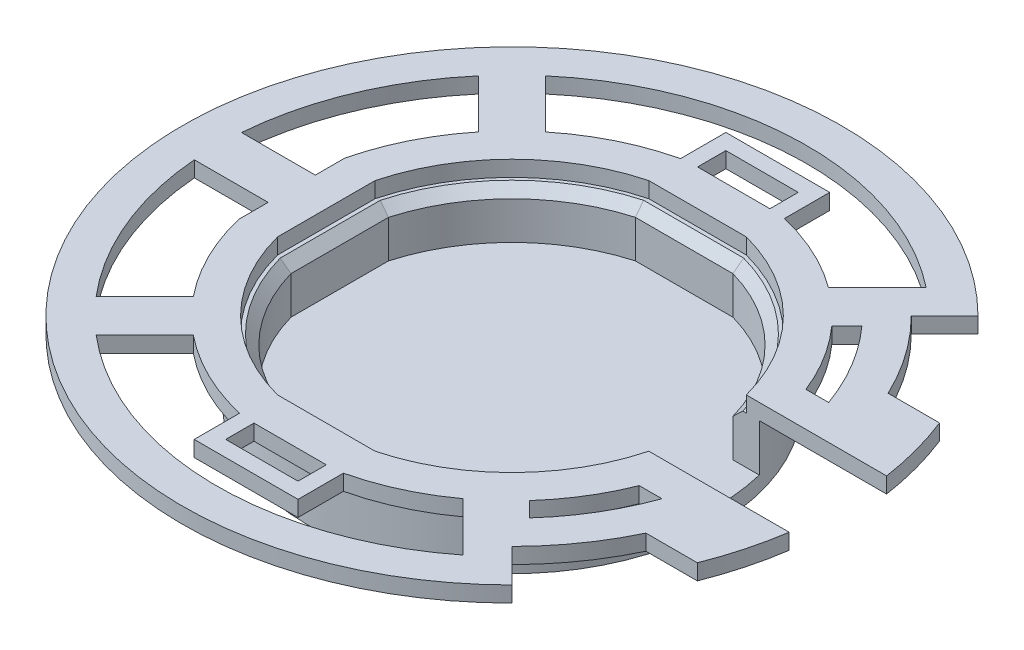
SolidWorks part; units mm, degrees
ref_plane "Front Plane" through (0, 0, 0) normal (0, 0, 1) x (1, 0, 0)
ref_plane "Top Plane" through (0, 0, 0) normal (0, 1, 0) x (1, 0, 0)
ref_plane "Right Plane" through (0, 0, 0) normal (1, 0, 0) x (0, 0, -1)
sketch "Front" plane through (0, 0, 0) normal (0, 0, 1) x (1, 0, 0)
  line L0 (0, 0) -> (0, 4407.3663) construction
  line L1 (0, 0) -> (4407.3663, 0) construction
  line L2 (0, 2.5) -> (-20.95, 2.5)
  line L3 (-20.95, 2.5) -> (-20.95, 1.5)
  line L4 (-20.95, 1.5) -> (-13, 1.5)
  line L5 (-13, 1.5) -> (-13, -2.5)
  line L6 (-13, -2.5) -> (0, -2.5)
  line L7 (0, -2.5) -> (0, 2.5)
  dimension "D1" = 1
  dimension "D2" = 41.9
  dimension "D3" = 5
  dimension "D4" = 26
sketch "Top" plane through (0, 0, 0) normal (0, 1, 0) x (1, 0, 0)
  line L0 (0, 0) -> (0, 50000) construction
  line L1 (0, 0) -> (50000, 0) construction
sketch "Right" plane through (0, 0, 0) normal (1, 0, 0) x (0, 0, -1)
  line L0 (0, 0) -> (0, 50000) construction
  line L1 (0, 0) -> (50000, 0) construction
revolve "Base" add sketch "Front" angle 360 about L0
sketch "Sketch2" plane through (0, 2.5, 0) normal (0, 1, 0) x (1, 0, 0)
  line L0 (0, 0) -> (50000, 0) construction
  line L1 (0, 0) -> (0, 50000) construction
  line L2 (-3.0984, 11.8) -> (3.0984, 11.8)
  line L3 (-11.8, -3.0984) -> (-11.8, 3.0984)
  line L4 (-3.0984, -11.8) -> (3.0984, -11.8)
  line L5 (11.8, -3.0984) -> (11.8, 3.0984)
  line L6 (-2.3, -14.1) -> (2.3, -14.1)
  line L7 (-2.3, 15.9) -> (2.3, 15.9)
  line L8 (-2.3, 15.9) -> (-2.3, 14.1)
  line L9 (-2.3, 14.1) -> (2.3, 14.1)
  line L10 (2.3, 15.9) -> (2.3, 14.1)
  line L11 (-2.3, 15.9) -> (2.3, 14.1) construction
  line L12 (-2.3, 14.1) -> (2.3, 15.9) construction
  line L13 (2.3, -15.9) -> (2.3, -14.1)
  line L14 (-2.3, -15.9) -> (2.3, -15.9)
  line L15 (-2.3, -15.9) -> (-2.3, -14.1)
  line L16 (-2.3, -14.1) -> (2.3, -15.9) construction
  line L17 (-2.3, -15.9) -> (2.3, -14.1) construction
  circle A0 centre (0, 0) radius 12.2 construction
  arc A1 (-11.8, 3.0984) -> (-3.0984, 11.8) centre (0, 0) cw
  arc A2 (-11.8, -3.0984) -> (-3.0984, -11.8) centre (0, 0) ccw
  arc A3 (11.8, -3.0984) -> (3.0984, -11.8) centre (0, 0) cw
  arc A4 (11.8, 3.0984) -> (3.0984, 11.8) centre (0, 0) ccw
  point P7 (0, 15)
  point P15 (-11.8, 0)
  point P16 (0, -11.8)
  point P19 (0, 11.8)
  point P28 (0, -15)
  dimension "D1" = 24.4
  dimension "D2" = 23.6
  dimension "D3" = 1.8
  dimension "D4" = 4.6
  dimension "D5" = 30
extrude "Watch Positioner" cut sketch "Sketch2" against normal up to surface (1 mm away) contours L5 A4 L2 A1 L3 A2 L4 A3 | L10 L7 L8 L9 | L15 L14 L13 L6 region at (0, 2.5, 0) region at (0, 2.5, 15) region at (0, 2.5, -15) up to face at (0, 1.5, -13)
sketch "Sketch4" plane through (0, 2.5, 0) normal (0, 1, 0) x (1, 0, 0)
  line L0 (3.0984, 11.8) -> (-3.0984, 11.8) construction
  line L1 (3.0984, 11.8) -> (-3.0984, 11.8) construction
  line L2 (-3.0984, 10.95) -> (-3.0984, 11.8) construction
  line L3 (3.0984, -10.95) -> (-3.0984, -10.95)
  line L4 (10.95, 3.0984) -> (10.95, -3.0984) construction
  line L5 (10.95, 3.0984) -> (21.95, 3.0984)
  line L6 (21.95, 3.0984) -> (21.95, -3.0984)
  line L7 (0, 0) -> (50000, 0) construction
  line L8 (0, 7.5051) -> (0, 50007.5051) construction
  line L9 (10.95, -3.0984) -> (21.95, -3.0984)
  line L10 (16.2153, 7.6984) -> (20.5557, 7.6984)
  line L12 (15.521, 15.521) -> (12.6926, 12.6926)
  line L13 (15.521, -15.521) -> (12.6926, -12.6926)
  line L14 (16.2153, -7.6984) -> (20.5557, -7.6984)
  line L15 (-10.95, 3.0984) -> (-10.95, -3.0984)
  line L18 (3.0984, 10.95) -> (-3.0984, 10.95)
  circle A0 centre (0, 0) radius 11.3799 construction
  arc A1 (-3.0984, -10.95) -> (-10.95, -3.0984) centre (0, 0) cw
  arc A2 (3.0984, -10.95) -> (10.95, -3.0984) centre (0, 0) ccw
  arc A3 (3.0984, 10.95) -> (10.95, 3.0984) centre (0, 0) cw
  arc A4 (15.521, 15.521) -> (20.5557, 7.6984) centre (0, 0) cw
  arc A5 (12.6926, -12.6926) -> (16.2153, -7.6984) centre (0, 0) ccw
  arc A6 (15.521, -15.521) -> (20.5557, -7.6984) centre (0, 0) ccw
  circle A7 centre (0, 0) radius 21.95
  circle A8 centre (0, 0) radius 21.95 construction
  arc A9 (12.6926, 12.6926) -> (16.2153, 7.6984) centre (0, 0) cw
  circle A10 centre (0, 0) radius 17.95
  circle A11 centre (0, 0) radius 17.95 construction
  arc A18 (-3.0984, 10.95) -> (-10.95, 3.0984) centre (0, 0) ccw
  point P13 (-10.95, 0)
  point P16 (0, -10.95)
  point P19 (0, 10.95)
  point P28 (21.95, 0)
  dimension "D1" = 22.7598
  dimension "D5" = 45
  dimension "D2" = 21.9
  dimension "D3" = 1
  dimension "D6" = 4.6
  dimension "D4" = 3
extrude "Watch Holder v2" cut sketch "Sketch4" against normal offset from surface (4 mm away) 1 up to face at (0, -2.5, -13)
chamfer "Chamfer1" distance 0.6 angle 45 7 edges at (8.0468, 1.5, 8.0468) (0, 1.5, 10.95) (-8.0468, 1.5, 8.0468) (-10.95, 1.5, 0) (-8.0468, 1.5, -8.0468) (0, 1.5, -10.95) (8.0468, 1.5, -8.0468)
sketch "Sketch5" plane through (0, 0, 0) normal (0, 1, 0) x (1, 0, 0)
  line L0 (3.3, 16.9) -> (3.3, 14.0168)
  line L1 (0, 0) -> (50000, 0) construction
  line L2 (0, 0) -> (0, 50000) construction
  line L6 (-14, 1.5) -> (-18.6899, 1.5)
  line L7 (0, 0) -> (35355.3391, -35355.3391) construction
  line L8 (0, 0) -> (35355.3391, 35355.3391) construction
  line L9 (9.4721, 12.5834) -> (8.5072, 11.6184)
  line L10 (8.5072, 11.6184) -> (10.7323, 9.6009) construction
  line L11 (10.7323, 9.6009) -> (11.6882, 10.5569)
  line L12 (-14.2764, 12.1551) -> (-11.1876, 9.0663)
  line L13 (-12.1551, 14.2764) -> (-9.0663, 11.1876)
  line L14 (-14.2764, -12.1551) -> (-11.1876, -9.0663)
  line L15 (-14, -1.5) -> (-14, -3.3705)
  line L16 (-14, -1.5) -> (-18.6899, -1.5)
  line L17 (9.4721, -12.5834) -> (11.611, -14.7223)
  line L18 (14.7591, -5.4984) -> (17.9257, -5.4984)
  line L19 (17.9858, -5.2984) -> (13.3898, -5.2984)
  line L20 (3.3705, -14) -> (-3.3705, -14)
  line L21 (-14, -3.3705) -> (-14, 3.3705)
  line L22 (-3.3705, 14) -> (3.3705, 14)
  line L23 (13.3898, 5.2984) -> (17.9858, 5.2984)
  line L24 (17.9257, 5.4984) -> (14.7591, 5.4984)
  line L25 (9.4721, 12.5834) -> (11.611, 14.7223)
  line L26 (11.611, -14.7223) -> (9.4721, -12.5834)
  line L30 (-14, 1.5) -> (-14, 3.3705)
  line L32 (13.3898, 5.2984) -> (14.832, 5.2984)
  line L34 (9.4721, 12.5834) -> (11.611, 14.7223)
  line L36 (9.4721, -12.5834) -> (8.5072, -11.6184)
  line L37 (3.3, -16.9) -> (3.3, -14.0168)
  line L38 (3.3, -16.9) -> (-3.3, -16.9)
  line L39 (-3.3, -16.9) -> (-3.3, -14.0168)
  line L40 (-12.1551, -14.2764) -> (-9.0663, -11.1876)
  line L41 (13.3898, -5.2984) -> (14.832, -5.2984)
  line L43 (10.7323, -9.6009) -> (11.6882, -10.5569)
  line L44 (-2.3, 15.9) -> (-3.3, 16.9) construction
  line L45 (2.3, 15.9) -> (2.3, 14.1) construction
  line L96 (-3.3, 16.9) -> (-3.3, 14.0168)
  line L97 (2.3, 15.9) -> (3.3, 16.9) construction
  line L104 (3.3, 16.9) -> (-3.3, 16.9)
  arc A0 (8.5072, 11.6184) -> (3.3, 14.0168) centre (0, 0) ccw
  arc A1 (-11.1876, 9.0663) -> (-14, 3.3705) centre (0, 0) ccw
  arc A2 (-14.2764, 12.1551) -> (-18.6899, 1.5) centre (0, 0) ccw
  arc A3 (-11.1876, -9.0663) -> (-14, -3.3705) centre (0, 0) cw
  arc A4 (-14.2764, -12.1551) -> (-18.6899, -1.5) centre (0, 0) cw
  arc A5 (8.5072, -11.6184) -> (3.3, -14.0168) centre (0, 0) cw
  arc A6 (-3.3, -14.0168) -> (-9.0663, -11.1876) centre (0, 0) cw
  arc A7 (11.611, -14.7223) -> (-12.1551, -14.2764) centre (0, 0) cw
  arc A8 (13.3898, -5.2984) -> (10.7323, -9.6009) centre (0, 0) cw
  arc A10 (14.832, -5.2984) -> (11.6882, -10.5569) centre (0, 0) cw
  arc A18 (9.4721, -12.5834) -> (14.7591, -5.4984) centre (0, 0) ccw
  arc A19 (17.9257, -5.4984) -> (17.9858, -5.2984) centre (0, 0) ccw
  arc A20 (3.3705, -14) -> (13.3898, -5.2984) centre (0, 0) ccw
  arc A21 (-14, -3.3705) -> (-3.3705, -14) centre (0, 0) ccw
  arc A22 (-3.3705, 14) -> (-14, 3.3705) centre (0, 0) ccw
  arc A23 (13.3898, 5.2984) -> (3.3705, 14) centre (0, 0) ccw
  arc A24 (17.9858, 5.2984) -> (17.9257, 5.4984) centre (0, 0) ccw
  arc A25 (14.7591, 5.4984) -> (9.4721, 12.5834) centre (0, 0) ccw
  arc A26 (11.611, 14.7223) -> (11.611, -14.7223) centre (0, 0) ccw
  arc A31 (-3.3, 14.0168) -> (-9.0663, 11.1876) centre (0, 0) ccw
  arc A32 (13.3898, 5.2984) -> (10.7323, 9.6009) centre (0, 0) ccw
  arc A34 (14.832, 5.2984) -> (11.6882, 10.5569) centre (0, 0) ccw
  arc A35 (11.611, 14.7223) -> (-12.1551, 14.2764) centre (0, 0) ccw
  point P25 (0, 0)
  point P33 (2.8216, 16.4216)
  point P63 (3.9259, -13.5424)
  point P69 (-3.6918, -13.5424)
  dimension "D3" = 45
  dimension "D2" = 3
  dimension "D4" = 3
  dimension "D5" = 3
  dimension "D6" = 1
  dimension "D1" = 2.2
extrude "Cut-Extrude1" cut sketch "Sketch5" along normal through all both and the other way through all
